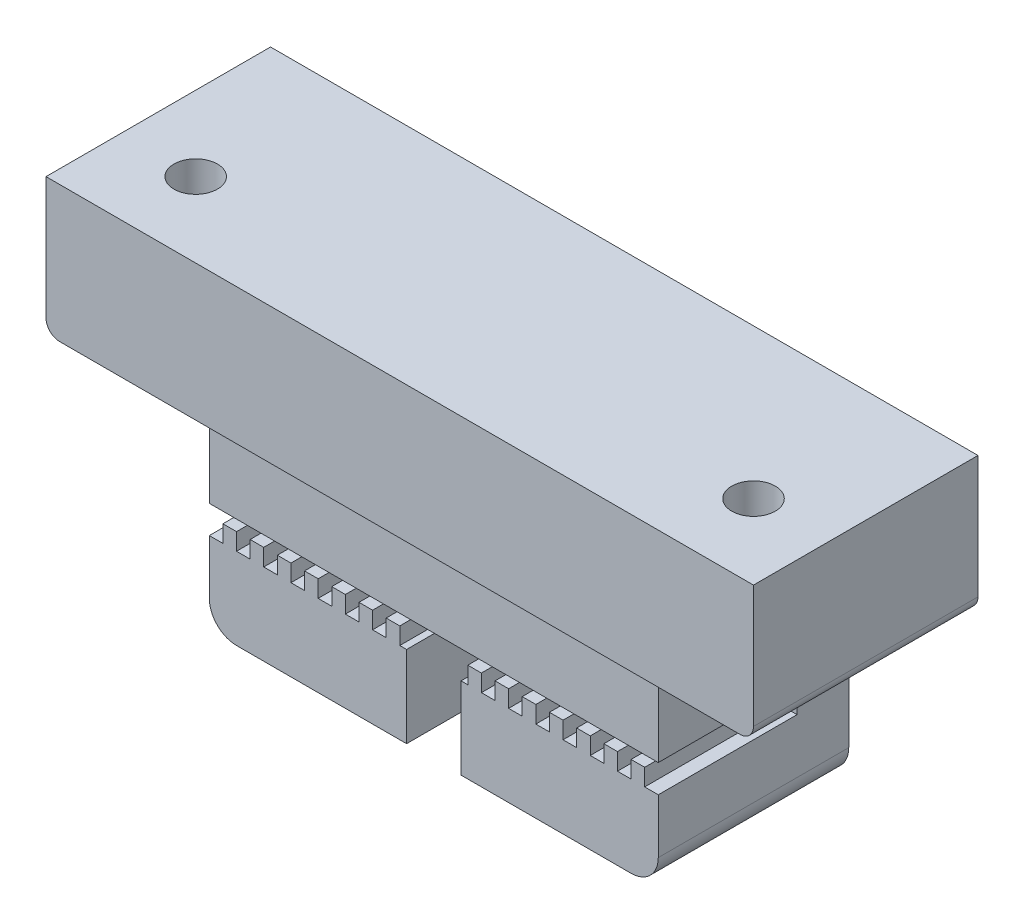
SolidWorks part; units mm, degrees
ref_plane "Plano frontal" through (0, 0, 0) normal (0, 0, 1) x (1, 0, 0)
ref_plane "Plano superior" through (0, 0, 0) normal (0, 1, 0) x (1, 0, 0)
ref_plane "Plano direito" through (0, 0, 0) normal (1, 0, 0) x (0, 0, -1)
sketch "Esboço1" plane through (0, 0, 0) normal (0, 0, 1) x (1, 0, 0)
  line L0 (-26, 25.35) -> (26, 25.35)
  line L1 (26, 25.35) -> (26, 16.35)
  line L2 (25, 15.35) -> (16.5, 15.35)
  line L3 (16.5, 15.35) -> (16.5, 2)
  line L4 (14.5, 0) -> (-14.5, 0)
  line L5 (-16.5, 2) -> (-16.5, 15.35)
  line L6 (-16.5, 15.35) -> (-25, 15.35)
  line L7 (-26, 16.35) -> (-26, 25.35)
  line L8 (0, 25.35) -> (0, 0) construction
  arc A0 (26, 16.35) -> (25, 15.35) centre (25, 16.35) cw
  arc A1 (-25, 15.35) -> (-26, 16.35) centre (-25, 16.35) cw
  arc A2 (16.5, 2) -> (14.5, 0) centre (14.5, 2) cw
  arc A3 (-14.5, 0) -> (-16.5, 2) centre (-14.5, 2) cw
  point P16 (16.5, 8.675)
  dimension "D1" = 1
  dimension "D2" = 2
  dimension "D3" = 52
  dimension "D4" = 33
  dimension "D5" = 15.35
  dimension "D6" = 10
extrude "Ressalto-extrusão1" add sketch "Esboço1" along normal blind 14
sketch "Esboço2" plane through (0, 0, 14) normal (0, 0, 1) x (1, 0, 0)
  line L0 (-26, 25.35) -> (26, 25.35)
  line L1 (26, 16.35) -> (26, 25.35) construction
  line L2 (-26, 25.35) -> (-26, 16.35) construction
  line L3 (26, 16.35) -> (26, 25.35)
  line L4 (-26, 25.35) -> (-26, 16.35)
  line L5 (-25, 15.35) -> (25, 15.35)
  arc A0 (25, 15.35) -> (26, 16.35) centre (25, 16.35) ccw construction
  arc A1 (-26, 16.35) -> (-25, 15.35) centre (-25, 16.35) ccw construction
  arc A2 (25, 15.35) -> (26, 16.35) centre (25, 16.35) ccw
  arc A3 (-26, 16.35) -> (-25, 15.35) centre (-25, 16.35) ccw
extrude "Ressalto-extrusão2" add sketch "Esboço2" along normal blind 5
sketch "Esboço3" plane through (0, 25.35, 0) normal (0, 1, 0) x (1, 0, 0)
  line L0 (-26, -11) -> (26, -11) construction
  line L3 (26, -19) -> (-26, -19) construction
  line L4 (-26, -19) -> (-26, 0) construction
  line L5 (26, -19) -> (26, 0) construction
  circle A0 centre (-20.5, -11) radius 1.6
  circle A1 centre (20.5, -11) radius 1.6
  dimension "D3" = 3.2
  dimension "D1" = 41
  dimension "D2" = 5.5
  dimension "D4" = 8
extrude "Corte-extrusão1" cut sketch "Esboço3" against normal through all
sketch "Esboço4" plane through (0, 15.35, 0) normal (0, -1, 0) x (1, 0, 0)
  circle A0 centre (-20.5, 11) radius 2.9
  circle A1 centre (20.5, 11) radius 2.9
  dimension "D1" = 5.8
extrude "Corte-extrusão2" cut sketch "Esboço4" against normal blind 4.5
fillet "Filete1" radius 2 3 edges at (16.5, 15.35, 7) (0, 15.35, 14) (-16.5, 15.35, 7)
sketch "Esboço5" plane through (0, 0, 14) normal (0, 0, 1) x (1, 0, 0)
  line L6 (-14.5, 0) -> (14.5, 0) construction
  line L7 (-15.5, 6) -> (-16.5, 6)
  line L8 (-16.5, 8.05) -> (-19.4654, 8.05)
  line L10 (-15.5, 6) -> (-15.5, 7.25)
  line L11 (-15.5, 7.25) -> (-14.5, 7.25)
  line L12 (-14.5, 7.25) -> (-14.5, 6)
  line L13 (-14.5, 6) -> (-13.5, 6)
  line L14 (-13.5, 6) -> (-13.5, 7.25)
  line L15 (-13.5, 7.25) -> (-12.5, 7.25)
  line L16 (-12.5, 7.25) -> (-12.5, 6)
  line L17 (-12.5, 6) -> (-11.5, 6)
  line L18 (-11.5, 6) -> (-11.5, 7.25)
  line L19 (-11.5, 7.25) -> (-10.5, 7.25)
  line L20 (-10.5, 7.25) -> (-10.5, 6)
  line L21 (-10.5, 6) -> (-9.5, 6)
  line L22 (-9.5, 6) -> (-9.5, 7.25)
  line L23 (-9.5, 7.25) -> (-8.5, 7.25)
  line L24 (-8.5, 7.25) -> (-8.5, 6)
  line L25 (-8.5, 6) -> (-7.5, 6)
  line L26 (-7.5, 6) -> (-7.5, 7.25)
  line L27 (-7.5, 7.25) -> (-6.5, 7.25)
  line L28 (-6.5, 7.25) -> (-6.5, 6)
  line L29 (-6.5, 6) -> (-5.5, 6)
  line L30 (-5.5, 6) -> (-5.5, 7.25)
  line L31 (-5.5, 7.25) -> (-4.5, 7.25)
  line L32 (-4.5, 7.25) -> (-4.5, 6)
  line L33 (-4.5, 6) -> (-3.5, 6)
  line L34 (-3.5, 6) -> (-3.5, 7.25)
  line L35 (-3.5, 7.25) -> (-2.5, 7.25)
  line L36 (-2.5, 7.25) -> (-2.5, 6)
  line L37 (-2.5, 6) -> (-2, 6)
  line L46 (-16.5, 8.05) -> (16.5, 8.05)
  line L52 (-19.4654, 8.05) -> (-19.4654, -4.7344)
  line L89 (-19.4654, -4.7344) -> (-16.5, -4.7344)
  line L90 (0, 11.15) -> (0, 0) construction
  line L91 (-16.5, 6) -> (-16.5, -4.7344)
  line L92 (-16.5, 11.15) -> (16.5, 11.15) construction
  line L93 (-16.5, 13.35) -> (-16.5, 2) construction
  line L94 (16.5, 2) -> (16.5, 13.35) construction
  line L95 (-2, 0) -> (2, 0)
  line L96 (-2, 6) -> (-2, 0)
  line L97 (16.5, 6) -> (16.5, -4.7344)
  line L98 (19.4654, -4.7344) -> (16.5, -4.7344)
  line L99 (19.4654, 8.05) -> (19.4654, -4.7344)
  line L100 (2, 6) -> (2, 0)
  line L101 (2.5, 6) -> (2, 6)
  line L102 (2.5, 7.25) -> (2.5, 6)
  line L103 (3.5, 7.25) -> (2.5, 7.25)
  line L104 (3.5, 6) -> (3.5, 7.25)
  line L105 (4.5, 6) -> (3.5, 6)
  line L106 (4.5, 7.25) -> (4.5, 6)
  line L107 (5.5, 7.25) -> (4.5, 7.25)
  line L108 (5.5, 6) -> (5.5, 7.25)
  line L109 (6.5, 6) -> (5.5, 6)
  line L110 (6.5, 7.25) -> (6.5, 6)
  line L111 (7.5, 7.25) -> (6.5, 7.25)
  line L112 (7.5, 6) -> (7.5, 7.25)
  line L113 (8.5, 6) -> (7.5, 6)
  line L114 (8.5, 7.25) -> (8.5, 6)
  line L115 (9.5, 7.25) -> (8.5, 7.25)
  line L116 (9.5, 6) -> (9.5, 7.25)
  line L117 (10.5, 6) -> (9.5, 6)
  line L118 (10.5, 7.25) -> (10.5, 6)
  line L119 (11.5, 7.25) -> (10.5, 7.25)
  line L120 (11.5, 6) -> (11.5, 7.25)
  line L121 (12.5, 6) -> (11.5, 6)
  line L122 (12.5, 7.25) -> (12.5, 6)
  line L123 (13.5, 7.25) -> (12.5, 7.25)
  line L124 (13.5, 6) -> (13.5, 7.25)
  line L125 (14.5, 6) -> (13.5, 6)
  line L126 (14.5, 7.25) -> (14.5, 6)
  line L127 (15.5, 7.25) -> (14.5, 7.25)
  line L128 (15.5, 6) -> (15.5, 7.25)
  line L129 (16.5, 8.05) -> (19.4654, 8.05)
  line L130 (15.5, 6) -> (16.5, 6)
  point P51 (0, 8.05)
  dimension "D1" = 6
  dimension "D2" = 0.8
extrude "Corte-extrusão3" cut sketch "Esboço5" against normal blind 10.2
sketch "Esboço6" plane through (-26, 0, 0) normal (1, 0, 0) x (0, 0, -1)
  line L0 (0, 20.85) -> (-19, 20.85) construction
  line L1 (0, 16.35) -> (0, 25.35) construction
  line L2 (-19, 16.35) -> (-19, 25.35) construction
  circle A0 centre (-4, 20.85) radius 1.5
  dimension "D1" = 3
  dimension "D2" = 4
extrude "Corte-extrusão5" cut sketch "Esboço6" along normal blind 10
sketch "Esboço7" plane through (26, 0, 0) normal (1, 0, 0) x (0, 0, -1)
  line L0 (-16.5032, 15.35) -> (-16.5032, 25.35)
  line L1 (-19, 15.35) -> (0, 15.35) construction
  line L2 (-19, 25.35) -> (0, 25.35) construction
  line L3 (-16.5032, 25.35) -> (-19, 25.35)
  line L4 (-19, 25.35) -> (-19, 15.35)
  line L5 (-19, 16.35) -> (-19, 15.35) construction
  line L6 (-19, 15.35) -> (-16.5032, 15.35)
  dimension "D1" = 2.4968
extrude "Corte-extrusão6" cut sketch "Esboço7" against normal through all both and the other way through all
